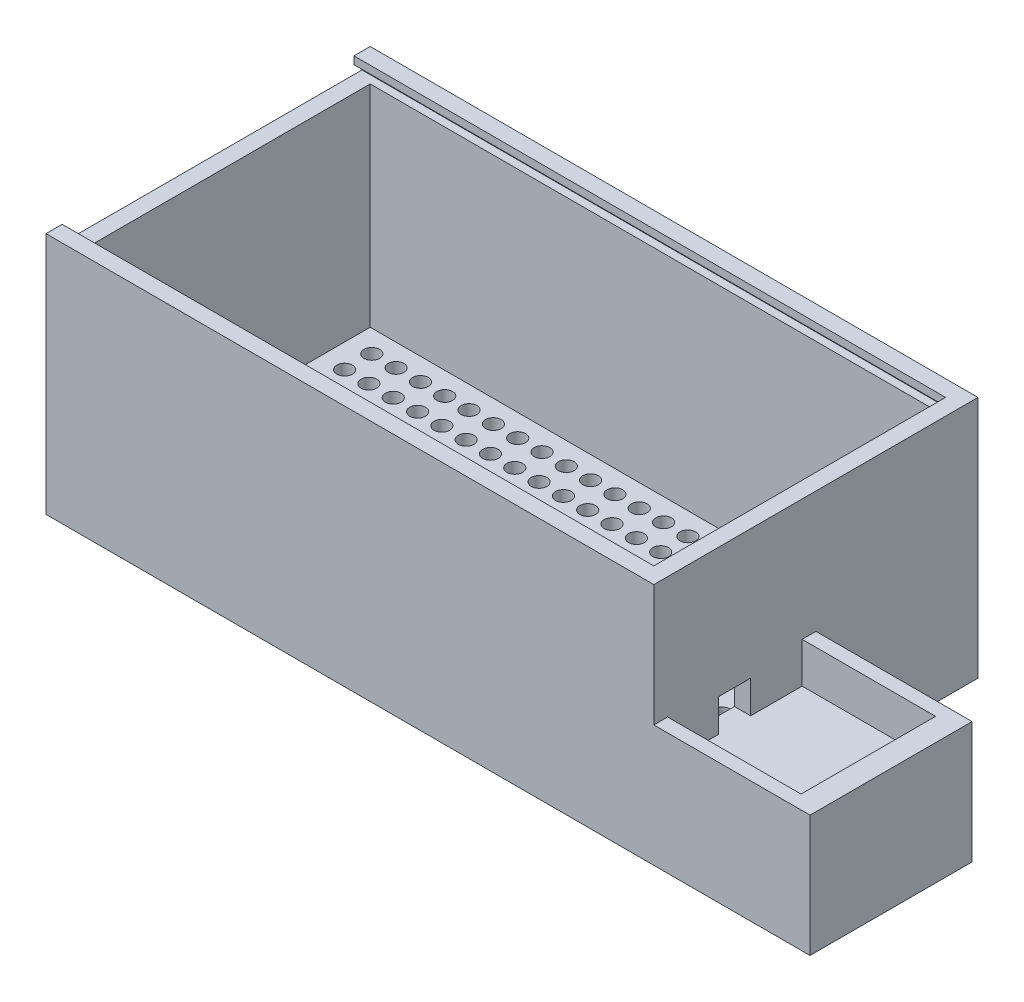
SolidWorks part; units mm, degrees
ref_plane "Front Plane" through (0, 0, 0) normal (0, 0, 1) x (1, 0, 0)
ref_plane "Top Plane" through (0, 0, 0) normal (0, 1, 0) x (1, 0, 0)
ref_plane "Right Plane" through (0, 0, 0) normal (1, 0, 0) x (0, 0, -1)
sketch "Sketch1" plane through (0, 0, 0) normal (0, 1, 0) x (1, 0, 0)
  line L0 (-38.7395, 56.242) -> (151.7605, 56.242)
  line L1 (151.7605, 56.242) -> (151.7605, -45.358)
  line L2 (151.7605, -45.358) -> (-38.7395, -45.358)
  line L3 (-38.7395, -45.358) -> (-38.7395, 56.242)
  dimension "D1" = 190.5
  dimension "D2" = 101.6
extrude "Boss-Extrude2" add sketch "Sketch1" along normal blind 76.2 contours L2 L3 L0 L1
sketch "Sketch3" plane through (0, 76.2, 0) normal (0, 1, 0) x (1, 0, 0)
  line L0 (-38.7395, 56.242) -> (151.7605, 56.242) construction
  line L9 (-33.6595, 51.162) -> (146.6805, 51.162)
  line L10 (-33.6595, 51.162) -> (-33.6595, -40.278)
  line L11 (-33.6595, -40.278) -> (146.6805, -40.278)
  line L12 (146.6805, 51.162) -> (146.6805, -40.278)
  line L13 (-38.7395, -45.358) -> (-38.7395, 56.242) construction
  line L15 (151.7605, -45.358) -> (-38.7395, -45.358) construction
  line L16 (151.7605, 56.242) -> (151.7605, -45.358) construction
  dimension "D1" = 5.08
  dimension "D2" = 5.08
  dimension "D3" = 5.08
  dimension "D4" = 5.08
extrude "Cut-Extrude2" cut sketch "Sketch3" against normal blind 71.12
sketch "Sketch5" plane through (0, 0, 0) normal (0, -1, 0) x (1, 0, 0)
  line L11 (151.7605, 45.358) -> (151.7605, -5.442)
  line L12 (151.7605, -56.242) -> (151.7605, 45.358) construction
  line L13 (151.7605, -5.442) -> (200.7116, -5.442)
  line L14 (200.7116, -5.442) -> (200.7116, 45.358)
  line L15 (200.7116, 45.358) -> (151.7605, 45.358)
sketch "Sketch9" plane through (-33.6595, 0, 0) normal (1, 0, 0) x (0, 0, -1)
  line L0 (51.162, 5.08) -> (-40.278, 5.08) construction
  circle A1 centre (-27.885, 13.8563) radius 4.9904
  point P4 (0, 0)
  point P5 (-31.404, 13.8563)
  point P6 (-27.885, 13.8563)
  dimension "D1" = 8.7763
extrude "Cut-Extrude12" cut sketch "Sketch9" against normal blind 5.08 contours A1
sketch "Sketch11" plane through (0, 0, 0) normal (0, -1, 0) x (-1, 0, 0)
sketch "Sketch12" plane through (0, 0, 0) normal (0, -1, 0) x (1, 0, 0)
  line L0 (-38.7395, 45.358) -> (-38.7395, -56.242) construction
  line L1 (151.7605, 45.358) -> (-38.7395, 45.358) construction
  circle A0 centre (-26.0395, 32.658) radius 2.4589
  circle A1 centre (-18.4195, 32.658) radius 2.4589
  circle A2 centre (-10.7995, 32.658) radius 2.4589
  circle A3 centre (-3.1795, 32.658) radius 2.4589
  circle A4 centre (4.4405, 32.658) radius 2.4589
  circle A5 centre (12.0605, 32.658) radius 2.4589
  circle A6 centre (19.6805, 32.658) radius 2.4589
  circle A7 centre (27.3005, 32.658) radius 2.4589
  circle A8 centre (34.9205, 32.658) radius 2.4589
  circle A9 centre (42.5405, 32.658) radius 2.4589
  circle A10 centre (50.1605, 32.658) radius 2.4589
  circle A11 centre (57.7805, 32.658) radius 2.4589
  circle A12 centre (65.4005, 32.658) radius 2.4589
  circle A13 centre (73.0205, 32.658) radius 2.4589
  circle A14 centre (80.6405, 32.658) radius 2.4589
  circle A15 centre (88.2605, 32.658) radius 2.4589
  circle A16 centre (95.8805, 32.658) radius 2.4589
  circle A17 centre (103.5005, 32.658) radius 2.4589
  circle A18 centre (111.1205, 32.658) radius 2.4589
  circle A19 centre (118.7405, 32.658) radius 2.4589
  circle A20 centre (126.3605, 32.658) radius 2.4589
  circle A21 centre (133.9805, 32.658) radius 2.4589
  circle A22 centre (-18.4347, 24.1195) radius 2.4589
  circle A23 centre (-10.8147, 24.1195) radius 2.4589
  circle A24 centre (-3.1947, 24.1195) radius 2.4589
  circle A25 centre (4.4253, 24.1195) radius 2.4589
  circle A26 centre (12.0453, 24.1195) radius 2.4589
  circle A27 centre (19.6653, 24.1195) radius 2.4589
  circle A28 centre (27.2853, 24.1195) radius 2.4589
  circle A29 centre (34.9053, 24.1195) radius 2.4589
  circle A30 centre (42.5253, 24.1195) radius 2.4589
  circle A31 centre (50.1453, 24.1195) radius 2.4589
  circle A32 centre (57.7653, 24.1195) radius 2.4589
  circle A33 centre (65.3853, 24.1195) radius 2.4589
  circle A34 centre (73.0053, 24.1195) radius 2.4589
  circle A35 centre (80.6253, 24.1195) radius 2.4589
  circle A36 centre (88.2453, 24.1195) radius 2.4589
  circle A37 centre (95.8653, 24.1195) radius 2.4589
  circle A38 centre (103.4853, 24.1195) radius 2.4589
  circle A39 centre (111.1053, 24.1195) radius 2.4589
  circle A40 centre (118.7253, 24.1195) radius 2.4589
  circle A41 centre (126.3453, 24.1195) radius 2.4589
  circle A42 centre (133.9653, 24.1195) radius 2.4589
  circle A43 centre (-18.4498, 15.5811) radius 2.4589
  circle A44 centre (-10.8298, 15.5811) radius 2.4589
  circle A45 centre (-3.2098, 15.5811) radius 2.4589
  circle A46 centre (4.4102, 15.5811) radius 2.4589
  circle A47 centre (12.0302, 15.5811) radius 2.4589
  circle A48 centre (19.6502, 15.5811) radius 2.4589
  circle A49 centre (27.2702, 15.5811) radius 2.4589
  circle A50 centre (34.8902, 15.5811) radius 2.4589
  circle A51 centre (42.5102, 15.5811) radius 2.4589
  circle A52 centre (50.1302, 15.5811) radius 2.4589
  circle A53 centre (57.7502, 15.5811) radius 2.4589
  circle A54 centre (65.3702, 15.5811) radius 2.4589
  circle A55 centre (72.9902, 15.5811) radius 2.4589
  circle A56 centre (80.6102, 15.5811) radius 2.4589
  circle A57 centre (88.2302, 15.5811) radius 2.4589
  circle A58 centre (95.8502, 15.5811) radius 2.4589
  circle A59 centre (103.4702, 15.5811) radius 2.4589
  circle A60 centre (111.0902, 15.5811) radius 2.4589
  circle A61 centre (118.7102, 15.5811) radius 2.4589
  circle A62 centre (126.3302, 15.5811) radius 2.4589
  circle A63 centre (133.9502, 15.5811) radius 2.4589
  circle A64 centre (-18.4649, 7.0426) radius 2.4589
  circle A65 centre (-10.8449, 7.0426) radius 2.4589
  circle A66 centre (-3.2249, 7.0426) radius 2.4589
  circle A67 centre (4.3951, 7.0426) radius 2.4589
  circle A68 centre (12.0151, 7.0426) radius 2.4589
  circle A69 centre (19.6351, 7.0426) radius 2.4589
  circle A70 centre (27.2551, 7.0426) radius 2.4589
  circle A71 centre (34.8751, 7.0426) radius 2.4589
  circle A72 centre (42.4951, 7.0426) radius 2.4589
  circle A73 centre (50.1151, 7.0426) radius 2.4589
  circle A74 centre (57.7351, 7.0426) radius 2.4589
  circle A75 centre (65.3551, 7.0426) radius 2.4589
  circle A76 centre (72.9751, 7.0426) radius 2.4589
  circle A77 centre (80.5951, 7.0426) radius 2.4589
  circle A78 centre (88.2151, 7.0426) radius 2.4589
  circle A79 centre (95.8351, 7.0426) radius 2.4589
  circle A80 centre (103.4551, 7.0426) radius 2.4589
  circle A81 centre (111.0751, 7.0426) radius 2.4589
  circle A82 centre (118.6951, 7.0426) radius 2.4589
  circle A83 centre (126.3151, 7.0426) radius 2.4589
  circle A84 centre (133.9351, 7.0426) radius 2.4589
  circle A85 centre (-18.4801, -1.4958) radius 2.4589
  circle A86 centre (-10.8601, -1.4958) radius 2.4589
  circle A87 centre (-3.2401, -1.4958) radius 2.4589
  circle A88 centre (4.3799, -1.4958) radius 2.4589
  circle A89 centre (11.9999, -1.4958) radius 2.4589
  circle A90 centre (19.6199, -1.4958) radius 2.4589
  circle A91 centre (27.2399, -1.4958) radius 2.4589
  circle A92 centre (34.8599, -1.4958) radius 2.4589
  circle A93 centre (42.4799, -1.4958) radius 2.4589
  circle A94 centre (50.0999, -1.4958) radius 2.4589
  circle A95 centre (57.7199, -1.4958) radius 2.4589
  circle A96 centre (65.3399, -1.4958) radius 2.4589
  circle A97 centre (72.9599, -1.4958) radius 2.4589
  circle A98 centre (80.5799, -1.4958) radius 2.4589
  circle A99 centre (88.1999, -1.4958) radius 2.4589
  circle A100 centre (95.8199, -1.4958) radius 2.4589
  circle A101 centre (103.4399, -1.4958) radius 2.4589
  circle A102 centre (111.0599, -1.4958) radius 2.4589
  circle A103 centre (118.6799, -1.4958) radius 2.4589
  circle A104 centre (126.2999, -1.4958) radius 2.4589
  circle A105 centre (133.9199, -1.4958) radius 2.4589
  circle A106 centre (-18.4952, -10.0342) radius 2.4589
  circle A107 centre (-10.8752, -10.0342) radius 2.4589
  circle A108 centre (-3.2552, -10.0342) radius 2.4589
  circle A109 centre (4.3648, -10.0342) radius 2.4589
  circle A110 centre (11.9848, -10.0342) radius 2.4589
  circle A111 centre (19.6048, -10.0342) radius 2.4589
  circle A112 centre (27.2248, -10.0342) radius 2.4589
  circle A113 centre (34.8448, -10.0342) radius 2.4589
  circle A114 centre (42.4648, -10.0342) radius 2.4589
  circle A115 centre (50.0848, -10.0342) radius 2.4589
  circle A116 centre (57.7048, -10.0342) radius 2.4589
  circle A117 centre (65.3248, -10.0342) radius 2.4589
  circle A118 centre (72.9448, -10.0342) radius 2.4589
  circle A119 centre (80.5648, -10.0342) radius 2.4589
  circle A120 centre (88.1848, -10.0342) radius 2.4589
  circle A121 centre (95.8048, -10.0342) radius 2.4589
  circle A122 centre (103.4248, -10.0342) radius 2.4589
  circle A123 centre (111.0448, -10.0342) radius 2.4589
  circle A124 centre (118.6648, -10.0342) radius 2.4589
  circle A125 centre (126.2848, -10.0342) radius 2.4589
  circle A126 centre (133.9048, -10.0342) radius 2.4589
  circle A127 centre (-18.5103, -18.5727) radius 2.4589
  circle A128 centre (-10.8903, -18.5727) radius 2.4589
  circle A129 centre (-3.2703, -18.5727) radius 2.4589
  circle A130 centre (4.3497, -18.5727) radius 2.4589
  circle A131 centre (11.9697, -18.5727) radius 2.4589
  circle A132 centre (19.5897, -18.5727) radius 2.4589
  circle A133 centre (27.2097, -18.5727) radius 2.4589
  circle A134 centre (34.8297, -18.5727) radius 2.4589
  circle A135 centre (42.4497, -18.5727) radius 2.4589
  circle A136 centre (50.0697, -18.5727) radius 2.4589
  circle A137 centre (57.6897, -18.5727) radius 2.4589
  circle A138 centre (65.3097, -18.5727) radius 2.4589
  circle A139 centre (72.9297, -18.5727) radius 2.4589
  circle A140 centre (80.5497, -18.5727) radius 2.4589
  circle A141 centre (88.1697, -18.5727) radius 2.4589
  circle A142 centre (95.7897, -18.5727) radius 2.4589
  circle A143 centre (103.4097, -18.5727) radius 2.4589
  circle A144 centre (111.0297, -18.5727) radius 2.4589
  circle A145 centre (118.6497, -18.5727) radius 2.4589
  circle A146 centre (126.2697, -18.5727) radius 2.4589
  circle A147 centre (133.8897, -18.5727) radius 2.4589
  circle A148 centre (-18.5255, -27.1111) radius 2.4589
  circle A149 centre (-10.9055, -27.1111) radius 2.4589
  circle A150 centre (-3.2855, -27.1111) radius 2.4589
  circle A151 centre (4.3345, -27.1111) radius 2.4589
  circle A152 centre (11.9545, -27.1111) radius 2.4589
  circle A153 centre (19.5745, -27.1111) radius 2.4589
  circle A154 centre (27.1945, -27.1111) radius 2.4589
  circle A155 centre (34.8145, -27.1111) radius 2.4589
  circle A156 centre (42.4345, -27.1111) radius 2.4589
  circle A157 centre (50.0545, -27.1111) radius 2.4589
  circle A158 centre (57.6745, -27.1111) radius 2.4589
  circle A159 centre (65.2945, -27.1111) radius 2.4589
  circle A160 centre (72.9145, -27.1111) radius 2.4589
  circle A161 centre (80.5345, -27.1111) radius 2.4589
  circle A162 centre (88.1545, -27.1111) radius 2.4589
  circle A163 centre (95.7745, -27.1111) radius 2.4589
  circle A164 centre (103.3945, -27.1111) radius 2.4589
  circle A165 centre (111.0145, -27.1111) radius 2.4589
  circle A166 centre (118.6345, -27.1111) radius 2.4589
  circle A167 centre (126.2545, -27.1111) radius 2.4589
  circle A168 centre (133.8745, -27.1111) radius 2.4589
  circle A169 centre (-18.5406, -35.6496) radius 2.4589
  circle A170 centre (-10.9206, -35.6496) radius 2.4589
  circle A171 centre (-3.3006, -35.6496) radius 2.4589
  circle A172 centre (4.3194, -35.6496) radius 2.4589
  circle A173 centre (11.9394, -35.6496) radius 2.4589
  circle A174 centre (19.5594, -35.6496) radius 2.4589
  circle A175 centre (27.1794, -35.6496) radius 2.4589
  circle A176 centre (34.7994, -35.6496) radius 2.4589
  circle A177 centre (42.4194, -35.6496) radius 2.4589
  circle A178 centre (50.0394, -35.6496) radius 2.4589
  circle A179 centre (57.6594, -35.6496) radius 2.4589
  circle A180 centre (65.2794, -35.6496) radius 2.4589
  circle A181 centre (72.8994, -35.6496) radius 2.4589
  circle A182 centre (80.5194, -35.6496) radius 2.4589
  circle A183 centre (88.1394, -35.6496) radius 2.4589
  circle A184 centre (95.7594, -35.6496) radius 2.4589
  circle A185 centre (103.3794, -35.6496) radius 2.4589
  circle A186 centre (110.9994, -35.6496) radius 2.4589
  circle A187 centre (118.6194, -35.6496) radius 2.4589
  circle A188 centre (126.2394, -35.6496) radius 2.4589
  circle A189 centre (133.8594, -35.6496) radius 2.4589
  circle A190 centre (-18.5557, -44.188) radius 2.4589
  circle A191 centre (-10.9357, -44.188) radius 2.4589
  circle A192 centre (-3.3157, -44.188) radius 2.4589
  circle A193 centre (4.3043, -44.188) radius 2.4589
  circle A194 centre (11.9243, -44.188) radius 2.4589
  circle A195 centre (19.5443, -44.188) radius 2.4589
  circle A196 centre (27.1643, -44.188) radius 2.4589
  circle A197 centre (34.7843, -44.188) radius 2.4589
  circle A198 centre (42.4043, -44.188) radius 2.4589
  circle A199 centre (50.0243, -44.188) radius 2.4589
  circle A200 centre (57.6443, -44.188) radius 2.4589
  circle A201 centre (65.2643, -44.188) radius 2.4589
  circle A202 centre (72.8843, -44.188) radius 2.4589
  circle A203 centre (80.5043, -44.188) radius 2.4589
  circle A204 centre (88.1243, -44.188) radius 2.4589
  circle A205 centre (95.7443, -44.188) radius 2.4589
  circle A206 centre (103.3643, -44.188) radius 2.4589
  circle A207 centre (110.9843, -44.188) radius 2.4589
  circle A208 centre (118.6043, -44.188) radius 2.4589
  circle A209 centre (126.2243, -44.188) radius 2.4589
  circle A210 centre (133.8443, -44.188) radius 2.4589
  circle A211 centre (-26.0547, 24.1195) radius 2.4589
  circle A212 centre (-26.0698, 15.5811) radius 2.4589
  circle A213 centre (-26.0849, 7.0426) radius 2.4589
  circle A214 centre (-26.1001, -1.4958) radius 2.4589
  circle A215 centre (-26.1152, -10.0342) radius 2.4589
  circle A216 centre (-26.1303, -18.5727) radius 2.4589
  circle A217 centre (-26.1455, -27.1111) radius 2.4589
  circle A218 centre (-26.1606, -35.6496) radius 2.4589
  circle A219 centre (-26.1757, -44.188) radius 2.4589
  dimension "D3" = 4.9178
  dimension "D4" = 10
  dimension "D1" = 12.7
  dimension "D2" = 12.7
extrude "Cut-Extrude13" cut sketch "Sketch12" against normal blind 7.62
extrude "Boss-Extrude4" add sketch "Sketch5" against normal blind 38.1 contours L13 L14 L15 L11
sketch "Sketch13" plane through (0, 38.1, 0) normal (0, 1, 0) x (1, 0, 0)
  line L0 (151.7605, -45.358) -> (151.7605, 5.442) construction
  line L1 (151.7605, 1.124) -> (193.5809, 1.124)
  line L2 (151.7605, 1.124) -> (151.7605, -41.04)
  line L3 (151.7605, -41.04) -> (193.5809, -41.04)
  line L4 (193.5809, 1.124) -> (193.5809, -41.04)
  line L6 (200.7116, -45.358) -> (151.7605, -45.358) construction
  line L7 (151.7605, 5.442) -> (200.7116, 5.442) construction
  dimension "D1" = 4.318
  dimension "D2" = 4.318
  dimension "D3" = 41.8204
extrude "Cut-Extrude14" cut sketch "Sketch13" against normal blind 12.7 contours L4 L3 L2 L1
sketch "Sketch14" plane through (151.7605, 0, 0) normal (1, 0, 0) x (0, 0, -1)
  line L0 (-19.958, 25.4) -> (-15.0044, 25.4)
  line L1 (1.124, 25.4) -> (-41.04, 25.4) construction
  line L2 (-15.0044, 25.4) -> (-15.0044, 35.6316)
  line L3 (-15.0044, 35.6316) -> (-25.0914, 35.6316)
  line L4 (-25.0914, 35.6316) -> (-25.0914, 25.4)
  line L5 (-25.0914, 25.4) -> (-19.958, 25.4)
extrude "Cut-Extrude15" cut sketch "Sketch14" against normal blind 12.7
sketch "Sketch15" plane through (-33.6595, 0, 0) normal (1, 0, 0) x (0, 0, -1)
  line L0 (-17.6653, 21.5029) -> (3.3347, 21.5029)
  line L1 (-17.6653, 13.8563) -> (-17.6653, 6.3563)
  line L2 (-17.6653, 13.8563) -> (-17.6653, 21.5029)
  line L3 (3.3347, 21.5029) -> (3.3347, 6.3563)
  line L4 (3.3347, 6.3563) -> (-17.6653, 6.3563)
  dimension "D1" = 7.5
  dimension "D2" = 21
extrude "Cut-Extrude16" cut sketch "Sketch15" against normal blind 19.558
sketch "Sketch16" plane through (0, 76.2, 0) normal (0, 1, 0) x (1, 0, 0)
  line L0 (-33.6595, 51.162) -> (-38.7395, 51.162)
  line L1 (-38.7395, -45.358) -> (-38.7395, 56.242) construction
  line L2 (-33.6595, -40.278) -> (-38.7395, -40.278)
  line L3 (-33.6595, 51.162) -> (-33.6595, -40.278)
  line L4 (-38.7395, -40.278) -> (-38.7395, 51.162)
extrude "Cut-Extrude17" cut sketch "Sketch16" against normal blind 5.08
sketch "Sketch17" plane through (-38.7395, 0, 0) normal (-1, 0, 0) x (0, 0, 1)
  line L4 (-51.162, 5.08) -> (-51.162, 76.2) construction
  line L5 (-51.162, 73.8075) -> (-51.162, 71.12)
  line L10 (40.278, 71.12) -> (40.278, 76.2) construction
  line L11 (40.278, 73.66) -> (40.278, 71.12)
  line L12 (40.278, 73.66) -> (42.8925, 73.66)
  line L13 (42.8925, 73.66) -> (42.8925, 71.12)
  line L14 (42.8925, 71.12) -> (40.278, 71.12)
  line L15 (-51.162, 73.8075) -> (-53.6731, 73.8075)
  line L16 (-53.6731, 73.8075) -> (-53.6731, 71.12)
  line L17 (-53.6731, 71.12) -> (-51.162, 71.12)
extrude "Cut-Extrude18" cut sketch "Sketch17" against normal blind 185.42
